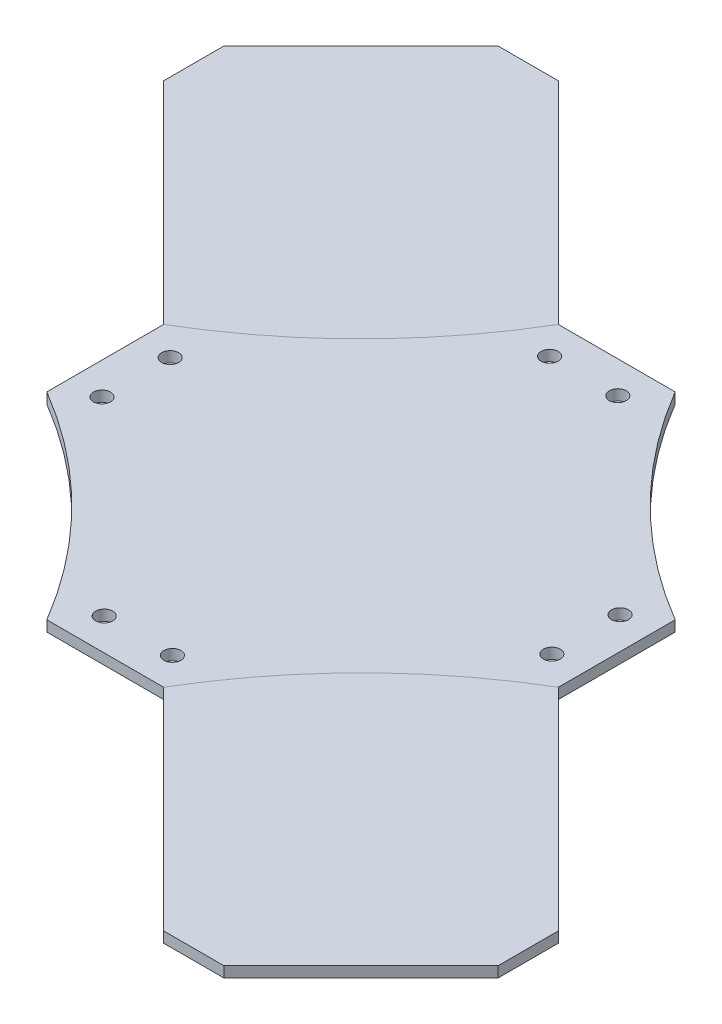
SolidWorks part; units mm, degrees
material "PE Low/Medium Density"
ref_plane "Front Plane" through (0, 0, 0) normal (0, 0, 1) x (1, 0, 0)
ref_plane "Top Plane" through (0, 0, 0) normal (0, 1, 0) x (1, 0, 0)
ref_plane "Right Plane" through (0, 0, 0) normal (1, 0, 0) x (0, 0, -1)
sketch "Sketch1" plane through (0, 0, 0) normal (0, 1, 0) x (1, 0, 0)
  line L0 (0, 0) -> (0, 60) construction
  line L1 (-13.7, 60) -> (13.7, 60)
  line L2 (60, 13.7) -> (60, -13.7)
  line L3 (13.7, -60) -> (-13.7, -60)
  line L4 (-60, -13.7) -> (-60, 13.7)
  line L5 (0, 0) -> (-75.007, 75.007) construction
  circle A0 centre (0, 0) radius 13.4565 construction
  arc A1 (-13.7, 60) -> (-60, 13.7) centre (-126.7477, 126.7477) cw
  arc A2 (60, 13.7) -> (13.7, 60) centre (126.7477, 126.7477) cw
  arc A3 (13.7, -60) -> (60, -13.7) centre (126.7477, -126.7477) cw
  arc A4 (-60, -13.7) -> (-13.7, -60) centre (-126.7477, -126.7477) cw
  point P8 (0, 60)
  point P17 (0, 0)
  point P28 (0, 0)
  point P29 (0, 0)
  point P30 (0, 0)
  dimension "D6" = 4
  dimension "D1" = 27.4
  dimension "D2" = 60
  dimension "D4" = 45
  dimension "D3" = 4
  dimension "D5" = 120
extrude "Boss-Extrude1" add sketch "Sketch1" along normal blind 2.5
sketch "Sketch2" plane through (0, 2.5, 0) normal (0, 1, 0) x (1, 0, 0)
  line L0 (0, 60) -> (0, -60) construction
  line L1 (13.7, 60) -> (-13.7, 60) construction
  line L2 (-13.7, -60) -> (13.7, -60) construction
sketch "Sketch3" plane through (0, 2.5, 0) normal (0, 1, 0) x (1, 0, 0)
  line L0 (13.7, 60) -> (-13.7, 60) construction
  circle A0 centre (-8.2597, 52.5) radius 2
  circle A1 centre (7.7403, 52.5) radius 2
  dimension "D1" = 4
  dimension "D2" = 4
  dimension "D3" = 16
  dimension "D4" = 7.5
extrude "Cut-Extrude1" cut sketch "Sketch3" against normal blind 2.5
ref_axis "Axis1" through (0, 0, 0) along (0, 1, 0)
pattern_circular "CirPattern1" count 4 over 360 about axis through (0, 0, 0) along (0, 1, 0) of "Cut-Extrude1"
sketch "Sketch4" plane through (0, 2.5, 0) normal (0, 1, 0) x (1, 0, 0)
  line L0 (0, 0) -> (-119.4032, 119.4032) construction
  line L1 (-60, 13.7) -> (-109.4975, 63.1975)
  line L2 (-13.7, 60) -> (-63.1975, 109.4975)
  line L3 (-77.3396, 109.4975) -> (-109.4975, 77.3396)
  line L4 (0, 0) -> (0, 174.825) construction
  line L5 (-109.4975, 63.1975) -> (-109.4975, 77.3396)
  line L6 (-63.1975, 109.4975) -> (-77.3396, 109.4975)
  arc A0 (-60, 13.7) -> (-13.7, 60) centre (-126.7477, 126.7477) ccw construction
  arc A1 (-60, 13.7) -> (-13.7, 60) centre (-126.7477, 126.7477) ccw
  point P4 (-116.5685, 70.2685)
  point P7 (-70.2685, 116.5685)
  dimension "D1" = 45
  dimension "D2" = 90
  dimension "D3" = 80
extrude "Boss-Extrude2" add sketch "Sketch4" against normal blind 2.5 separate body
ref_plane "Plane1" through (0, 0, 0) normal (-0.7071, 0, -0.7071) x (-0.7071, 0, 0.7071)
mirror "Mirror3" about plane through (0, 0, 0) normal (-0.7071, 0, -0.7071) of bodies 104
sketch "Sketch6" plane through (0, 0, 0) normal (0, -1, 0) x (1, 0, 0)
  line L0 (-52.5, 8.2597) -> (-52.5, -7.7403) construction
  line L2 (-56.1836, -13.1487) -> (-48.8164, -13.1487)
  line L3 (-56.1836, -13.1487) -> (-56.1836, 13.6681)
  line L4 (-56.1836, 13.6681) -> (-48.8164, 13.6681)
  line L5 (-48.8164, -13.1487) -> (-48.8164, 13.6681)
  line L6 (-56.1836, -13.1487) -> (-48.8164, 13.6681) construction
  line L7 (-56.1836, 13.6681) -> (-48.8164, -13.1487) construction
  point P4 (-52.5, 0.2597)
extrude "Boss-Extrude3" [suppressed] add sketch "Sketch6" along normal blind 50 separate body
sketch "Sketch7" [suppressed] plane through (0, -50, 0) normal (0, -1, 0) x (1, 0, 0)
  circle A0 centre (-52.5, 8.2597) radius 2 construction
  circle A1 centre (-52.5, 8.2597) radius 2
  circle A2 centre (-52.5, -7.7403) radius 2 construction
  circle A3 centre (-52.5, -7.7403) radius 2
extrude "Cut-Extrude2" [suppressed] cut sketch "Sketch7" against normal blind 25
pattern_circular "CirPattern4" [suppressed] count 4 over 360 about axis through (0, 0, 0) along (0, 1, 0) of bodies 110
